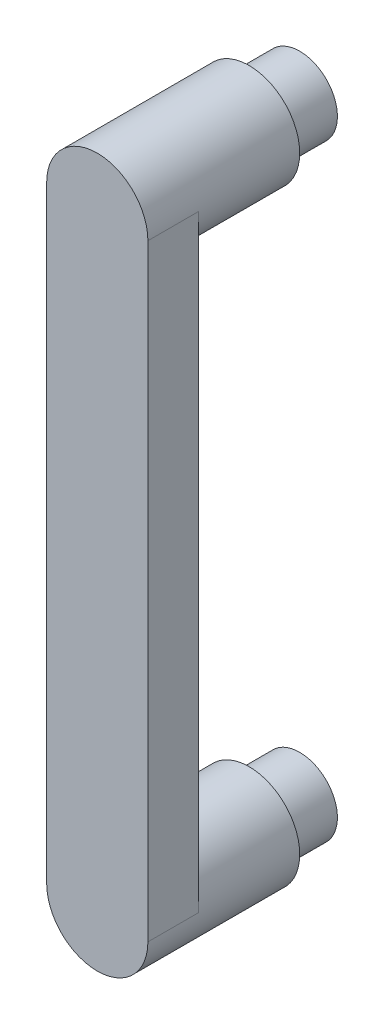
SolidWorks part; units mm, degrees
ref_plane "前视基准面" through (0, 0, 0) normal (0, 0, 1) x (1, 0, 0)
ref_plane "上视基准面" through (0, 0, 0) normal (0, 1, 0) x (1, 0, 0)
ref_plane "右视基准面" through (0, 0, 0) normal (1, 0, 0) x (0, 0, -1)
sketch "草图1" plane through (0, 0, 0) normal (0, 0, 1) x (1, 0, 0)
  circle A0 centre (0, 0) radius 1.49
  dimension "D1" = 2.98
extrude "凸台-拉伸1" add sketch "草图1" along normal blind 4
sketch "草图2" plane through (0, 0, 0) normal (0, 0, -1) x (-1, 0, 0)
  circle A0 centre (0, 0) radius 2
  dimension "D1" = 4
extrude "凸台-拉伸2" add sketch "草图2" along normal blind 4
sketch "草图3" plane through (0, 0, 4) normal (0, 0, 1) x (1, 0, 0)
  circle A0 centre (0, 0) radius 2
  dimension "D1" = 4
extrude "凸台-拉伸3" add sketch "草图3" along normal blind 4
sketch "草图4" plane through (0, 0, 0) normal (0, 1, 0) x (1, 0, 0)
  line L0 (2, 4) -> (-2, 4) construction
  line L1 (-2, 4) -> (2, 4)
  line L2 (-2, 4) -> (-2, 6)
  line L3 (-2, 6) -> (2, 6)
  line L4 (2, 4) -> (2, 6)
  dimension "D1" = 2
extrude "凸台-拉伸4" add sketch "草图4" along normal blind 12 and the other way up to surface other way up to face at (-2, 0, -4)
sketch "草图6" plane through (0, 0, 0) normal (0, 1, 0) x (1, 0, 0)
  line L1 (-2, -8) -> (2, -8)
  line L2 (-2, -8) -> (-2, -10)
  line L3 (-2, -10) -> (2, -10)
  line L4 (2, -8) -> (2, -10)
  dimension "D1" = 2
extrude "凸台-拉伸5" add sketch "草图6" along normal blind 12 and the other way up to surface other way up to face at (2, 0, 8)
ref_plane "基准面4" through (0, 12, 0) normal (0, 1, 0) x (1, 0, 0)
mirror "镜向2" about plane through (0, 12, 0) normal (0, 1, 0) of bodies 105
sketch "草图7" plane through (0, 0, 0) normal (1, 0, 0) x (0, 0, -1)
  line L5 (-10, 26) -> (6, 26) construction
  line L6 (6, -2) -> (6, 0) construction
  line L7 (-2, 26) -> (6, 26)
  line L8 (-2, 26) -> (-2, -2)
  line L9 (-2, -2) -> (6, -2)
  line L10 (6, 26) -> (6, -2)
extrude "切除-拉伸1" cut sketch "草图7" against normal blind 12 and the other way blind 12
sketch "草图8" plane through (0, 0, 2) normal (0, 0, -1) x (-1, 0, 0)
  circle A0 centre (0, 24) radius 1.025
  circle A1 centre (0, 0) radius 1.025
  dimension "D1" = 2.05
  dimension "D2" = 2.05
extrude "切除-拉伸2" cut sketch "草图8" against normal blind 2
